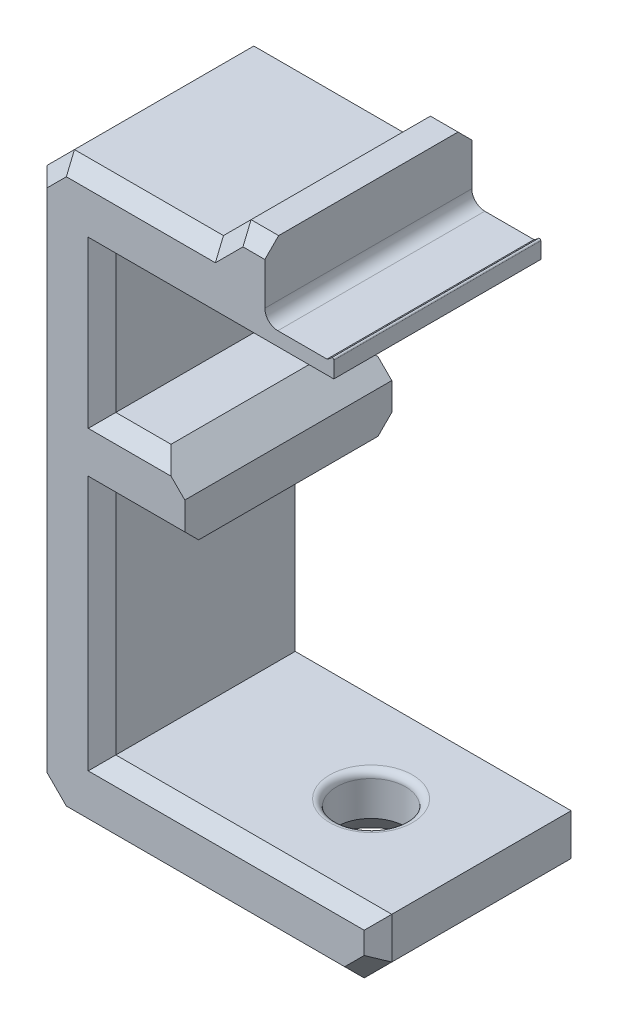
SolidWorks part; units mm, degrees
ref_plane "Plano frontal" through (0, 0, 0) normal (0, 0, 1) x (1, 0, 0)
ref_plane "Plano superior" through (0, 0, 0) normal (0, 1, 0) x (1, 0, 0)
ref_plane "Plano direito" through (0, 0, 0) normal (1, 0, 0) x (0, 0, -1)
sketch "Esboço1" plane through (0, 0, 0) normal (0, 0, 1) x (1, 0, 0)
  line L0 (11, 14.25) -> (-5.8, 14.25)
  line L1 (0.2, -0.75) -> (-5.8, -0.75)
  line L2 (-5.8, 14.25) -> (-5.8, 4.25)
  line L3 (-5.8, -17.25) -> (14.2, -17.25)
  line L4 (14.2, -17.25) -> (14.2, -22.25)
  line L5 (14.2, -22.25) -> (-10.8, -22.25)
  line L6 (-10.8, -22.25) -> (-10.8, 19.25)
  line L7 (0.2, 4.25) -> (0.2, -0.75)
  line L8 (0.2, 4.25) -> (-5.8, 4.25)
  line L9 (-5.8, -0.75) -> (-5.8, -17.25)
  line L10 (11, 14.25) -> (11, 16.25)
  line L11 (10.5044, 16.25) -> (6, 16.25)
  line L12 (6, 16.25) -> (6, 19.25)
  line L13 (6, 19.25) -> (-10.8, 19.25)
  line L14 (11, 16.25) -> (11, 16.4263)
  arc A0 (11, 16.4263) -> (10.8262, 16.4939) centre (10.9, 16.4263) ccw
  arc A1 (10.5044, 16.25) -> (10.8262, 16.4939) centre (10, 17.25) ccw
  dimension "D12" = 0.1
  dimension "D1" = 5
  dimension "D2" = 20
  dimension "D3" = 16.5
  dimension "D4" = 6
  dimension "D5" = 5
  dimension "D6" = 5
  dimension "D7" = 2
  dimension "D8" = 5
  dimension "D9" = 10
  dimension "D10" = 16.8
  dimension "D11" = 5
  dimension "D13" = 0.1763
  dimension "D14" = 0.4956
extrude "Ressalto-extrusão1" add sketch "Esboço1" along normal blind 15
sketch "Esboço3" plane through (0, -22.25, 0) normal (0, -1, 0) x (1, 0, 0)
  line L0 (14.2, 7.5) -> (6.2, 7.5) construction
  line L1 (14.2, 15) -> (14.2, 0) construction
  circle A0 centre (6.2, 7.5) radius 2.5
  dimension "D1" = 5
  dimension "D2" = 8
extrude "Corte-extrusão1" cut sketch "Esboço3" against normal blind 15
chamfer "Chanfro1" distance 2 angle 45 1 edges at (6.2, -22.25, 5)
fillet "Filete1" radius 0.5 1 edges at (6.2, -17.25, 5)
fillet "Filete2" radius 0.94 1 edges at (6, 16.25, 7.5)
sketch "Esboço5" plane through (0, 0, 15) normal (0, 0, 1) x (1, 0, 0)
  line L0 (6, 19.25) -> (6, 21.25)
  line L1 (6, 21.25) -> (4, 21.25)
  line L2 (4, 21.25) -> (2, 19.25)
  line L3 (6, 19.25) -> (-10.8, 19.25) construction
  line L4 (2, 19.25) -> (6, 19.25)
  dimension "D1" = 135
  dimension "D2" = 2
  dimension "D3" = 2
extrude "Ressalto-extrusão3" add sketch "Esboço5" against normal up to surface (15 mm away) up to face at (2.7124, 4.5565, 0)
chamfer "Chanfro5" distance 2 angle 45 4 edges at (14.2, -22.25, 7.5) (-10.8, -22.25, 7.5) (-10.8, 19.25, 7.5) (0.2, 4.25, 7.5)
chamfer "Chanfro4" distance 1 angle 45 31 edges at (-5.8, -9, 0) (-5.8, -9, 15) (-5.8, 9.25, 0) (-5.8, 9.25, 15) (2.6, 14.25, 0) (2.6, 14.25, 15) (11, 14.25, 7.5) (-3.8, 4.25, 0) (-3.8, 4.25, 15) (4.2, -17.25, 0) (4.2, -17.25, 15) (-2.8, -0.75, 0) (-2.8, -0.75, 15) (5, 21.25, 0) (3, 20.25, 0) (-3.4, 19.25, 0) (-9.8, 18.25, 0) (-10.8, -1.5, 0) (-9.8, -21.25, 0) (1.7, -22.25, 0) (13.2, -21.25, 0) (14.2, -18.75, 0) (5, 21.25, 15) (3, 20.25, 15) (-3.4, 19.25, 15) (-9.8, 18.25, 15) (-10.8, -1.5, 15) (-9.8, -21.25, 15) (1.7, -22.25, 15) (13.2, -21.25, 15) (14.2, -18.75, 15)
